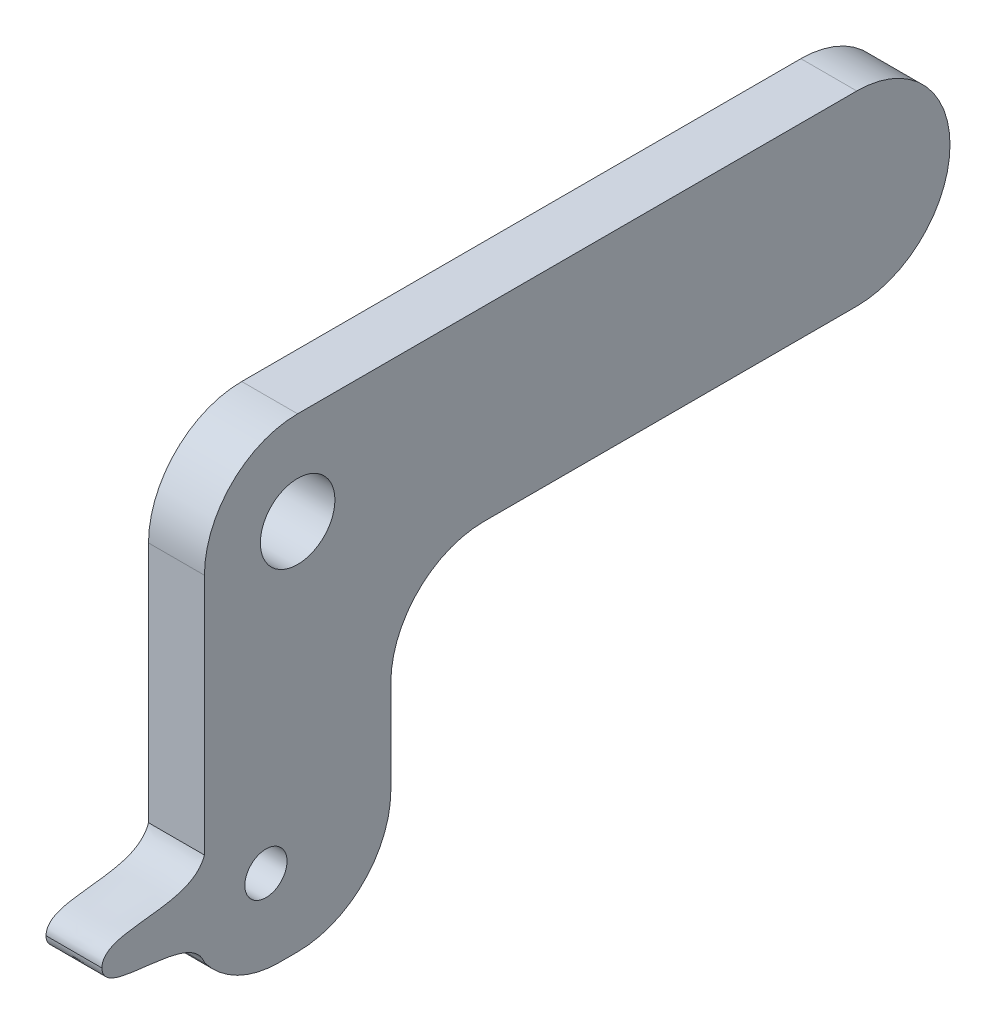
SolidWorks part; units mm, degrees
material "PC High Viscosity"
ref_plane "Front Plane" through (0, 0, 0) normal (0, 0, 1) x (1, 0, 0)
ref_plane "Top Plane" through (0, 0, 0) normal (0, 1, 0) x (1, 0, 0)
ref_plane "Right Plane" through (0, 0, 0) normal (1, 0, 0) x (0, 0, -1)
sketch "Sketch1" plane through (0, 0, 0) normal (1, 0, 0) x (0, 0, -1)
  line L0 (-5, 5) -> (35, 5)
  line L1 (35, 5) -> (35, -5)
  line L2 (35, -5) -> (5, -5)
  line L3 (5, -5) -> (5, -20)
  line L4 (5, -20) -> (-5, -20)
  line L5 (-5, -20) -> (-5, 5)
  line L7 (-5, 5) -> (0, 5) construction
  line L8 (-5, 5) -> (-5, 0) construction
  line L9 (-5, 0) -> (0, 0) construction
  line L10 (0, 5) -> (0, 0) construction
  circle A0 centre (0, 0) radius 2
  dimension "D2" = 4
  dimension "D1" = 10
  dimension "D3" = 5
  dimension "D4" = 40
  dimension "D5" = 25
extrude "Boss-Extrude1" add sketch "Sketch1" along normal blind 3
sketch "Sketch2" plane through (3, 0, 0) normal (1, 0, 0) x (0, 0, -1)
  line L0 (5, -15.5) -> (-15.8839, -15.5) construction
  line L1 (5, -20) -> (5, -5) construction
  line L2 (15.5, 10.3871) -> (15.5, -26.278) construction
  circle A0 centre (0, 0) radius 2 construction
  circle A1 centre (-1.7, -15.5) radius 1.1303
  dimension "D1" = 15.5
  dimension "D2" = 2.2606
  dimension "D3" = 15.5
  dimension "D4" = 17.2
extrude "Cut-Extrude1" cut sketch "Sketch2" against normal through all contours A1
sketch "Sketch3" plane through (3, 0, 0) normal (1, 0, 0) x (0, 0, -1)
  line L0 (5, -15.5) -> (-5, -15.5) construction
  line L1 (5, -20) -> (5, -5) construction
  line L2 (-5, 5) -> (-5, -20) construction
  line L3 (-5, -18) -> (-5, -13)
  spline S0 degree 3 poles (-5, -13) (-5.7214, -15.0822) (-10.4557, -13.77) (-10.4993, -15.5) knots 0 0 0 0 1 1 1 1
  spline S1 degree 3 poles (-5, -18) (-5.7214, -15.9178) (-10.4557, -17.23) (-10.4993, -15.5) knots 0 0 0 0 1 1 1 1
  dimension "D1" = 2.5
extrude "Boss-Extrude4" add sketch "Sketch3" against normal up to surface (3 mm away) up to face at (0, -15.5, 0.5697)
fillet "Fillet1" radius 5 6 edges at (1.5, -20, -5) (1.5, -5, -35) (1.5, 5, -35) (1.5, 5, 5) (1.5, -5, -5) (1.5, -20, 5)
equation "\"pulley_pitch_diam\"= 12.73mm"
equation "\"pulley_total_width\"= 16mm"
equation "\"pulley_total_diam\"= 16mm"
equation "\"belt_width\"= 6mm"
equation "\"material_thickness\"= 3mm"
equation "\"shaft_diam\"= 8mm"
equation "\"bearing_od\"= 22mm"
equation "\"bearing_thickness\"= 7mm"
equation "\"D1@Boss-Extrude1\"=\"material_thickness\""
